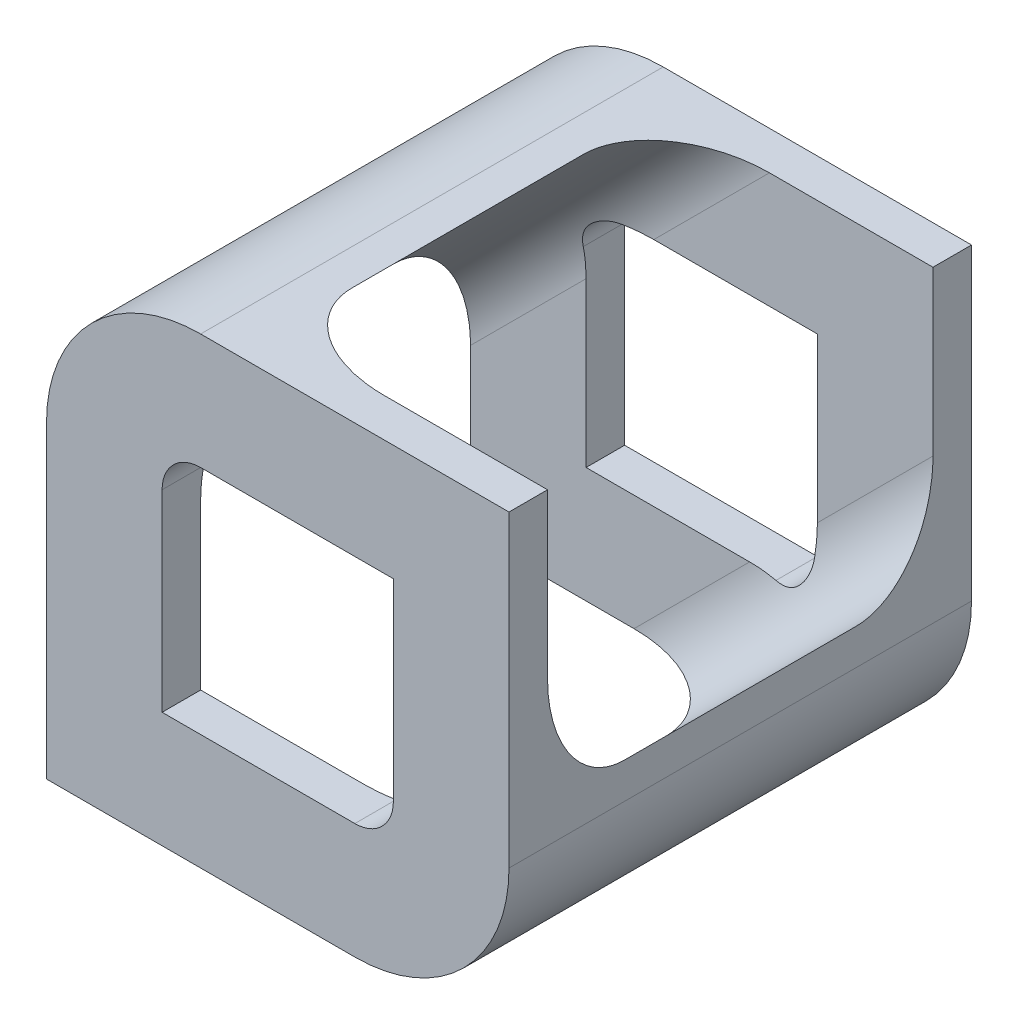
SolidWorks part; units mm, degrees
ref_plane "Front Plane" through (0, 0, 0) normal (0, 0, 1) x (1, 0, 0)
ref_plane "Top Plane" through (0, 0, 0) normal (0, 1, 0) x (1, 0, 0)
ref_plane "Right Plane" through (0, 0, 0) normal (1, 0, 0) x (0, 0, -1)
sketch "Sketch1" plane through (0, 0, 0) normal (0, 0, 1) x (1, 0, 0)
  line L0 (0, 0) -> (0, 50.8)
  line L1 (25.4, 76.2) -> (76.2, 76.2)
  line L2 (76.2, 76.2) -> (76.2, 25.4)
  line L3 (50.8, 0) -> (0, 0)
  line L5 (25.4, 57.15) -> (57.15, 57.15)
  line L6 (19.05, 50.8) -> (19.05, 19.05)
  line L7 (19.05, 19.05) -> (50.8, 19.05)
  line L8 (57.15, 57.15) -> (57.15, 25.4)
  arc A0 (0, 50.8) -> (25.4, 76.2) centre (25.4, 50.8) cw
  arc A1 (76.2, 25.4) -> (50.8, 0) centre (50.8, 25.4) cw
  arc A2 (25.4, 57.15) -> (19.05, 50.8) centre (25.4, 50.8) ccw
  arc A3 (57.15, 25.4) -> (50.8, 19.05) centre (50.8, 25.4) cw
  point P7 (0, 76.2)
  point P10 (76.2, 0)
  dimension "D3" = 25.4
  dimension "D4" = 25.4
  dimension "D6" = 6.35
  dimension "D7" = 6.35
  dimension "D8" = 19.05
  dimension "D1" = 76.2
  dimension "D2" = 76.2
  dimension "D5" = 19.05
  dimension "D9" = 19.05
  dimension "D10" = 19.05
extrude "Boss-Extrude2" add sketch "Sketch1" along normal blind 76.2 contours L0 A0 L1 L2 A1 L3
extrude "Cut-Extrude1" cut sketch "Sketch1<5>" along normal blind 76.2 contours L6 L7 A3 L8 L5 A2
sketch "Sketch1<5>" plane through (0, 0, 0) normal (0, 0, 1) x (1, 0, 0) same geometry as "Sketch1"
ref_plane "Plane2" through (76.2, 76.2, 0) normal (0.7071, 0.7071, 0) x (0, 0, -1)
sketch "Sketch6" plane through (76.2, 76.2, 0) normal (0.7071, 0.7071, 0) x (0, 0, -1)
  line L0 (-76.2, 0) -> (-76.2, -35.921) construction
  line L1 (-19.05, -31.75) -> (-57.15, -31.75)
  line L2 (-6.35, -19.05) -> (-6.35, 19.05)
  line L4 (-69.85, -19.05) -> (-69.85, 19.05)
  line L5 (-57.15, 31.75) -> (-19.05, 31.75)
  line L6 (-76.2, 0) -> (0, 0) construction
  arc A0 (-19.05, -31.75) -> (-6.35, -19.05) centre (-19.05, -19.05) ccw
  arc A1 (-69.85, -19.05) -> (-57.15, -31.75) centre (-57.15, -19.05) ccw
  arc A2 (-57.15, 31.75) -> (-69.85, 19.05) centre (-57.15, 19.05) ccw
  arc A3 (-6.35, 19.05) -> (-19.05, 31.75) centre (-19.05, 19.05) ccw
  point P14 (-69.85, 0)
  point P17 (0, 0)
  dimension "D1" = 12.7
  dimension "D2" = 12.7
  dimension "D3" = 12.7
  dimension "D4" = 12.7
  dimension "D5" = 63.5
  dimension "D6" = 63.5
  dimension "D7" = 6.35
extrude "Cut-Extrude6" cut sketch "Sketch6" against normal blind 204.978 contours L5 A3 L2 A0 L1 A1 L4 A2
